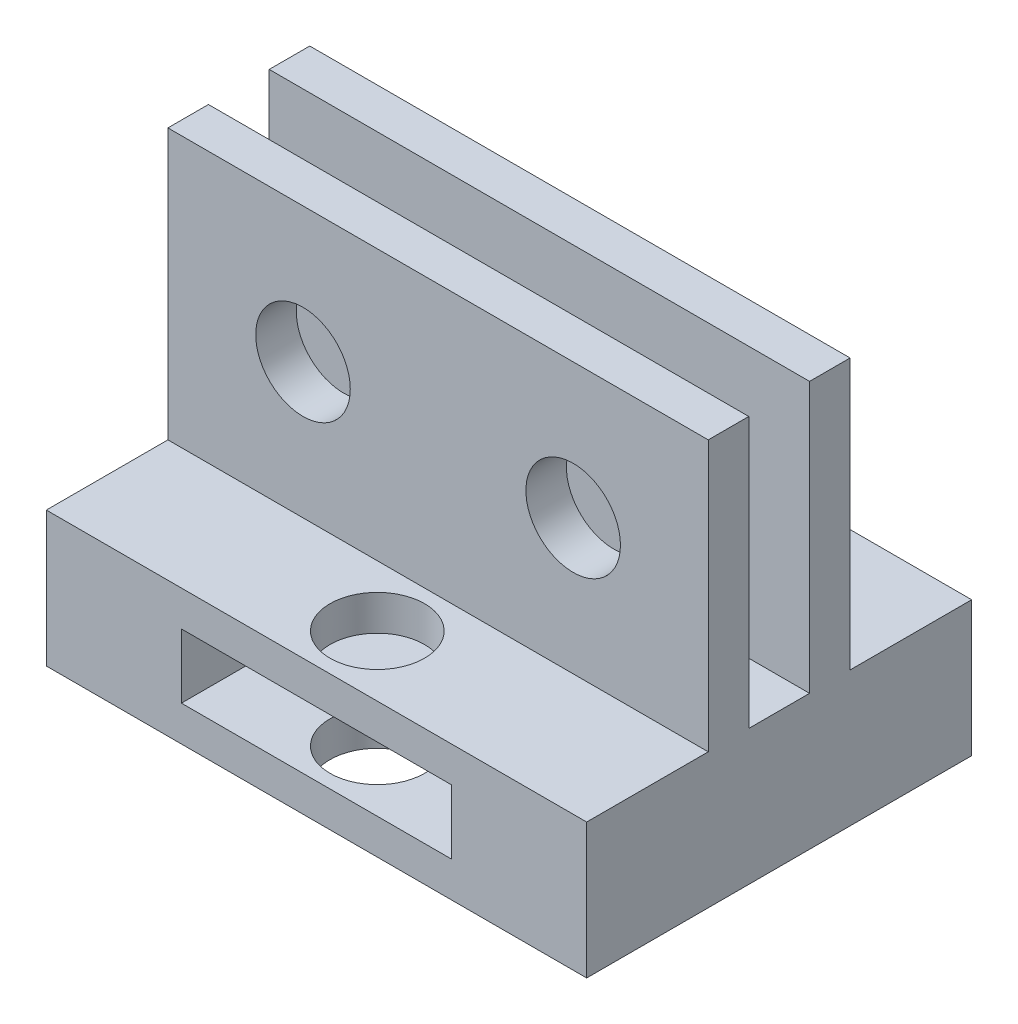
SolidWorks part; units mm, degrees
ref_plane "Front Plane" through (0, 0, 0) normal (0, 0, 1) x (1, 0, 0)
ref_plane "Top Plane" through (0, 0, 0) normal (0, 1, 0) x (1, 0, 0)
ref_plane "Right Plane" through (0, 0, 0) normal (1, 0, 0) x (0, 0, -1)
sketch "Sketch1" plane through (0, 0, 0) normal (0, 0, 1) x (1, 0, 0)
  line L1 (-296.042, -120) -> (-0.042, -120) construction
  line L2 (-6.342, -100) -> (-46.342, -100)
  line L3 (-6.342, -100) -> (-6.342, -120)
  line L4 (-6.342, -120) -> (-46.342, -120)
  line L5 (-46.342, -100) -> (-46.342, -120)
  line L7 (-6.342, -120) -> (-46.342, -120)
  line L8 (-6.342, -120) -> (-6.342, -130)
  line L9 (-6.342, -130) -> (-46.342, -130)
  line L10 (-46.342, -120) -> (-46.342, -130)
  line L11 (-36.342, -122.62) -> (-16.342, -122.62)
  line L12 (-36.342, -122.62) -> (-36.342, -127.38)
  line L13 (-36.342, -127.38) -> (-16.342, -127.38)
  line L14 (-16.342, -122.62) -> (-16.342, -127.38)
  circle A0 centre (-16.342, -110) radius 3.5
  circle A1 centre (-36.342, -110) radius 3.5
  circle A2 centre (-16.342, -110) radius 3.5 construction
  circle A3 centre (-36.342, -110) radius 3.5 construction
  point P22 (-16.342, -125)
  dimension "D1" = 10
  dimension "D2" = 10
  dimension "D3" = 10
  dimension "D4" = 10
  dimension "D5" = 4.76
  dimension "D6" = 5
extrude "Boss-Extrude1" add sketch "Sketch1" along normal blind 3 contours L2 L5 L4 L3 A1 A0 | L4 L10 L9 L8 L11 L14 L13 L12 region at (-26.342, -110, 0) region at (-6.7543, -125, 0)
extrude "Boss-Extrude3" add sketch "Sketch1<5>" against normal blind 7.5 contours L2 L5 L4 L3 A1 A0 | L4 L10 L9 L8 L11 L14 L13 L12 region at (-26.342, -110, 0) region at (-6.7543, -125, 0)
sketch "Sketch1<5>" plane through (0, 0, 0) normal (0, 0, 1) x (1, 0, 0) same geometry as "Sketch1"
extrude "Cut-Extrude1" cut sketch "Sketch1<6>" against normal blind 4.5 contours L2 L5 L4 L3 A1 A0 region at (-26.342, -110, 0)
sketch "Sketch1<6>" plane through (0, 0, 0) normal (0, 0, 1) x (1, 0, 0) same geometry as "Sketch1"
extrude "Boss-Extrude4" add sketch "Sketch1<7>" along normal blind 12 and the other way blind 16.5 contours L4 L10 L9 L8 L11 L14 L13 L12 region at (-6.7543, -125, 0)
sketch "Sketch1<7>" plane through (0, 0, 0) normal (0, 0, 1) x (1, 0, 0) same geometry as "Sketch1"
sketch "Sketch5" plane through (0, -130, 0) normal (0, -1, 0) x (1, 0, 0)
  line L0 (-6.342, 12) -> (-46.342, 12) construction
  line L1 (-26.342, 12) -> (-26.342, 7.5)
  line L2 (-26.342, -12) -> (-26.342, -16.5)
  line L3 (-6.342, -16.5) -> (-46.342, -16.5) construction
  circle A0 centre (-26.342, 7.5) radius 3.5
  circle A1 centre (-26.342, -12) radius 3.5
  dimension "D1" = 7
  dimension "D2" = 7
  dimension "D3" = 4.5
  dimension "D4" = 4.5
extrude "Cut-Extrude2" cut sketch "Sketch5" against normal blind 10 contours A0 | A1 region at (-28.7469, -130, 5.0951) region at (-23.9371, -130, -14.4049)
